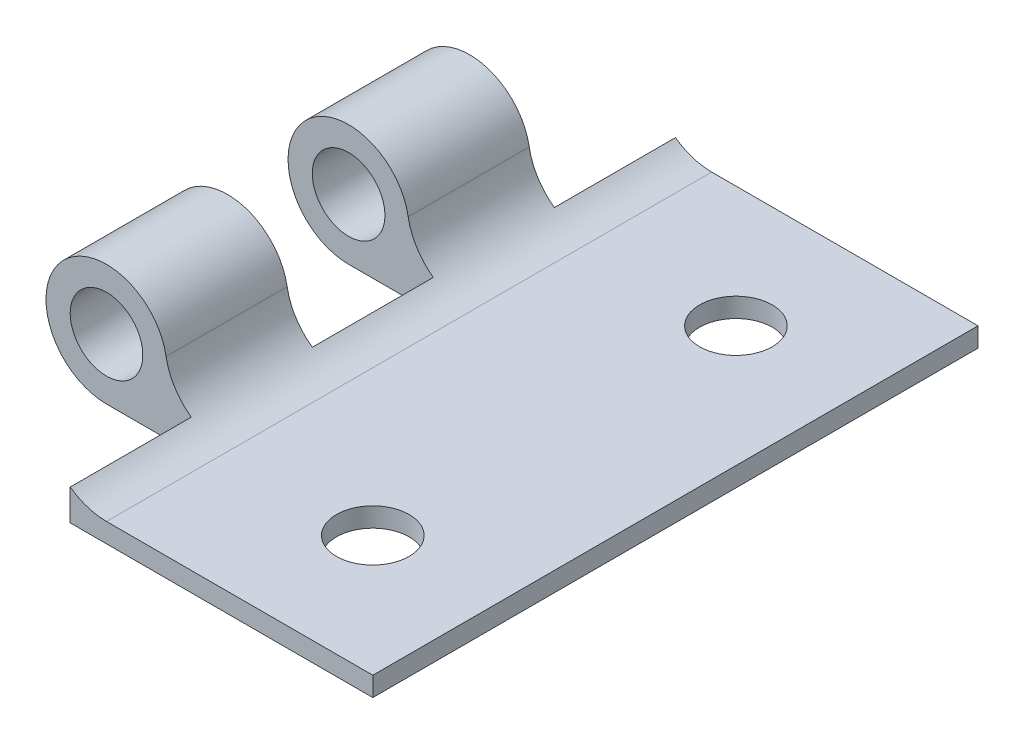
SolidWorks part; units mm, degrees
material "Aço cromo inoxidável"
ref_plane "Plano frontal" through (0, 0, 0) normal (0, 0, 1) x (1, 0, 0)
ref_plane "Plano superior" through (0, 0, 0) normal (0, 1, 0) x (1, 0, 0)
ref_plane "Plano direito" through (0, 0, 0) normal (1, 0, 0) x (0, 0, -1)
sketch "Esboço1" plane through (0, 0, 0) normal (0, 0, 1) x (1, 0, 0)
  line L0 (0, 0) -> (-16, 0)
  line L2 (-11, 0.8) -> (0, 0.8)
  line L3 (0, 0.8) -> (0, 0)
  arc A0 (-16, 0) -> (-14.2893, 4.323) centre (-16, 2.5) cw
  arc A1 (-14.2893, 4.323) -> (-13.5375, 2.9315) centre (-16, 2.5) cw
  arc A2 (-13.5375, 2.9315) -> (-11, 0.8) centre (-11, 3.3762) ccw
  circle A3 centre (-16, 2.5) radius 1.5
  point P10 (-14.2893, 4.323)
  dimension "D4" = 16
  dimension "D5" = 1
  dimension "D2" = 3
  dimension "D1" = 0.8
  dimension "D3" = 5
extrude "Ressalto-extrusão1" add sketch "Esboço1" along normal blind 25
sketch "Esboço2" plane through (0, 0, 0) normal (0, -1, 0) x (1, 0, 0)
  line L0 (-18.5, 25) -> (-18.5, 0) construction
  line L1 (-18.5, 0) -> (-12.5, 0)
  line L2 (-18.5, 0) -> (-18.5, 5)
  line L3 (-18.5, 5) -> (-12.5, 5)
  line L4 (-12.5, 0) -> (-12.5, 5)
  line L5 (0, 25) -> (0, 0) construction
  line L6 (-18.5, 0) -> (-13.5375, 0) construction
  line L7 (-18.5, 10) -> (-18.5, 15)
  line L8 (-18.5, 10) -> (-12.5, 10)
  line L9 (-12.5, 10) -> (-12.5, 15)
  line L10 (-18.5, 15) -> (-12.5, 15)
  line L11 (-18.5, 20) -> (-18.5, 25)
  line L12 (-18.5, 20) -> (-12.5, 20)
  line L13 (-12.5, 20) -> (-12.5, 25)
  line L14 (-18.5, 25) -> (-12.5, 25)
  line L15 (0, 12.5) -> (-9.0945, 12.5) construction
  line L16 (0, 25) -> (-11, 25) construction
  circle A0 centre (-5, 20) radius 1.5
  circle A1 centre (-5, 5) radius 1.5
  dimension "D5" = 3
  dimension "D1" = 5
  dimension "D2" = 3
  dimension "D3" = 5
  dimension "D4" = 6
  dimension "D6" = 5
  dimension "D7" = 5
extrude "Corte-extrusão2" cut sketch "Esboço2" against normal through all
